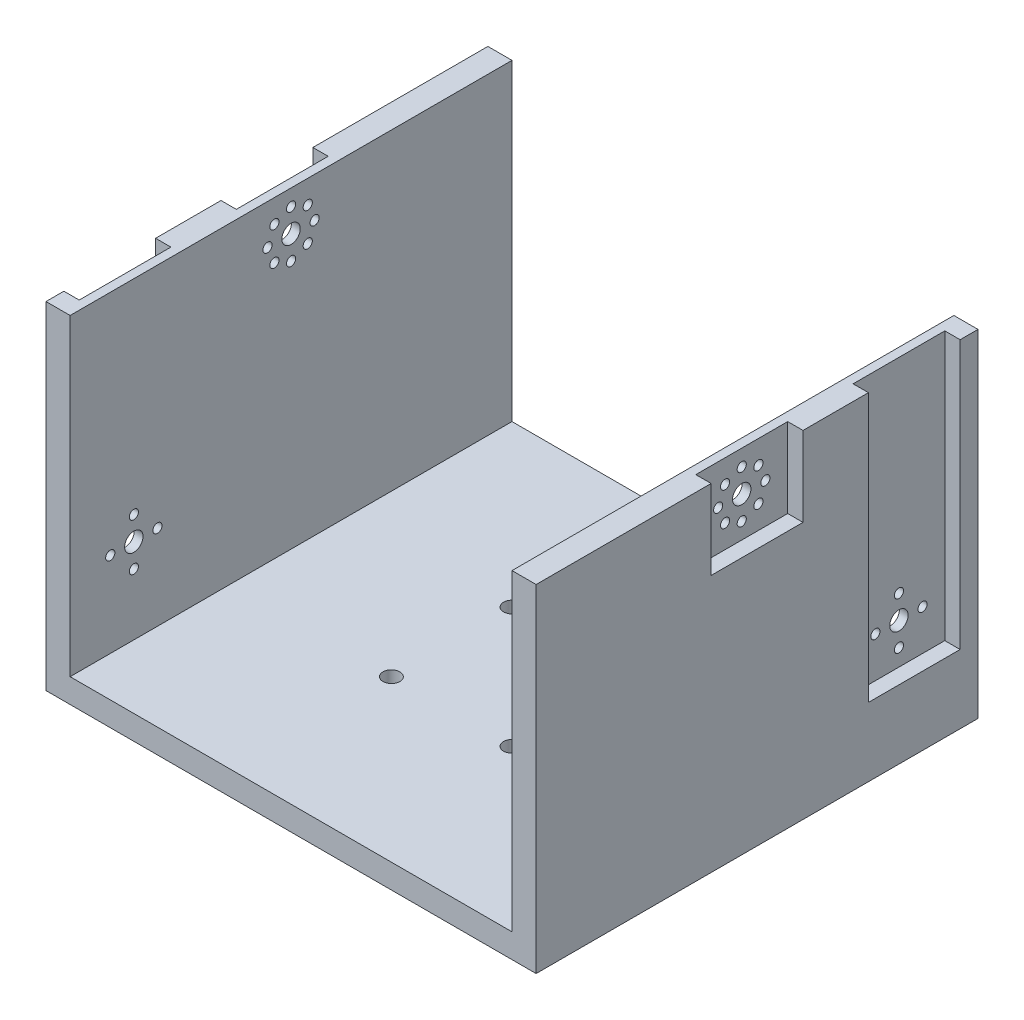
SolidWorks part; units mm, degrees
ref_plane "Front" through (0, 0, 0) normal (0, 0, 1) x (1, 0, 0)
ref_plane "Top" through (0, 0, 0) normal (0, 1, 0) x (1, 0, 0)
ref_plane "Right" through (0, 0, 0) normal (1, 0, 0) x (0, 0, -1)
sketch "Sketch2" plane through (0, 0, 0) normal (0, 1, 0) x (1, 0, 0)
  line L1 (-91.6, -91.6) -> (91.6, -91.6)
  line L2 (-91.6, -91.6) -> (-91.6, 91.6)
  line L3 (-91.6, 91.6) -> (91.6, 91.6)
  line L4 (91.6, -91.6) -> (91.6, 91.6)
  line L5 (-91.6, -91.6) -> (91.6, 91.6) construction
  line L6 (-91.6, 91.6) -> (91.6, -91.6) construction
  point P0 (0, 0)
  dimension "D1" = 183.2
extrude "Boss-Extrude1" add sketch "Sketch2" along normal blind 10
sketch "Sketch3" plane through (0, 0, 0) normal (0, 1, 0) x (1, 0, 0)
  line L0 (-91.6, -91.6) -> (91.6, -91.6) construction
  line L1 (-91.6, 91.6) -> (-101.6, 91.6)
  line L2 (-91.6, 91.6) -> (-91.6, -91.6)
  line L3 (-91.6, -91.6) -> (-101.6, -91.6)
  line L4 (-101.6, 91.6) -> (-101.6, -91.6)
  line L5 (0, 0) -> (0, 91.6) construction
  line L6 (91.6, 91.6) -> (-91.6, 91.6) construction
  line L7 (101.6, 91.6) -> (101.6, -91.6)
  line L8 (91.6, -91.6) -> (101.6, -91.6)
  line L9 (91.6, 91.6) -> (91.6, -91.6)
  line L10 (91.6, 91.6) -> (101.6, 91.6)
  dimension "D1" = 10
extrude "Boss-Extrude2" add sketch "Sketch3" along normal blind 139.7
sketch "Sketch4" plane through (0, 10, 0) normal (0, 1, 0) x (1, 0, 0)
  point P4 (0, 0)
hole_wizard "M6 Clearance Hole1" positions "Sketch5" profile "Sketch6" hole size "M6" standard "ANSI Metric" end condition up to next
sketch "Sketch5" plane through (0, 10, 0) normal (0, 1, 0) x (1, 0, 0)
  line L0 (0, 0) -> (0, 25) construction
  line L1 (0, 25) -> (-25, 25) construction
  line L3 (0, 25) -> (25, 25) construction
  point P0 (-25, 25)
  point P13 (25, 25)
  point P14 (25, -25)
  point P15 (-25, -25)
  dimension "D1" = 25
  dimension "D2" = 4
sketch "Sketch6" plane through (-25, 10, -25) normal (1, 0, 0) x (0, 0, 1)
  line L0 (0, 0) -> (0, 10)
  line L1 (0, 10) -> (3.5, 10)
  line L2 (3.5, 10) -> (3.5, 0)
  line L5 (3.5, 0) -> (0, 0)
  line L11 (0, -6.35) -> (0, 107.95) construction
  dimension "Thru Hole Dia." = 7
  dimension "Thru Hole Depth" = 10
sketch "Sketch7" plane through (91.6, 0, 0) normal (-1, 0, 0) x (0, 0, 1)
  line L0 (-91.6, 139.7) -> (91.6, 139.7) construction
  line L1 (0, 123.19) -> (0, 132.969) construction
  line L2 (0, 123.19) -> (0, 132.969) construction
  circle A0 centre (0, 123.19) radius 3.81
  circle A1 centre (0, 132.969) radius 1.8987
  circle A2 centre (6.9148, 130.1048) radius 1.8987
  circle A3 centre (9.779, 123.19) radius 1.8987
  circle A4 centre (6.9148, 116.2752) radius 1.8987
  circle A5 centre (0, 113.411) radius 1.8987
  circle A6 centre (-6.9148, 116.2752) radius 1.8987
  circle A7 centre (-9.779, 123.19) radius 1.8987
  circle A8 centre (-6.9148, 130.1048) radius 1.8987
  point P7 (0, 139.7)
  dimension "D1" = 7.62
  dimension "D3" = 3.7973
  dimension "D2" = 16.51
  dimension "D6" = 9.779
  dimension "D5" = 8
extrude "Cut-Extrude1" cut sketch "Sketch7" against normal through all both and the other way through all
sketch "Sketch8" plane through (0, 139.7, 0) normal (0, 1, 0) x (1, 0, 0)
  line L1 (95.25, -19.05) -> (101.6, -19.05)
  line L2 (95.25, -19.05) -> (95.25, 19.05)
  line L3 (95.25, 19.05) -> (101.6, 19.05)
  line L4 (101.6, -19.05) -> (101.6, 19.05)
  line L5 (95.25, -19.05) -> (101.6, 19.05) construction
  line L6 (95.25, 19.05) -> (101.6, -19.05) construction
  line L9 (101.6, -91.6) -> (101.6, 91.6) construction
  line L10 (0, 0) -> (0, 91.6) construction
  line L11 (91.6, 91.6) -> (-91.6, 91.6) construction
  line L13 (-95.25, 19.05) -> (-101.6, -19.05) construction
  line L14 (-95.25, -19.05) -> (-101.6, 19.05) construction
  line L16 (-101.6, -19.05) -> (-101.6, 19.05)
  line L17 (-95.25, 19.05) -> (-101.6, 19.05)
  line L18 (-95.25, -19.05) -> (-95.25, 19.05)
  line L19 (-95.25, -19.05) -> (-101.6, -19.05)
  point P0 (98.425, 0)
  point P12 (101.6, 0)
  point P23 (-98.425, 0)
  dimension "D1" = 38.1
  dimension "D2" = 6.35
extrude "Cut-Extrude2" cut sketch "Sketch8" against normal blind 33.02
sketch "Sketch9" plane through (101.6, 0, 0) normal (1, 0, 0) x (0, 0, -1)
  line L0 (48.666, 28.486) -> (54.762, 28.486) construction
  line L2 (84.186, 62.024) -> (84.186, 28.476)
  line L3 (84.186, 28.476) -> (46.166, 28.476)
  line L4 (46.166, 62.024) -> (46.166, 28.476)
  line L5 (84.186, 62.024) -> (46.166, 28.476) construction
  line L6 (84.186, 28.476) -> (46.166, 62.024) construction
  line L7 (48.666, 37.63) -> (48.666, 28.486) construction
  line L13 (84.186, 62.024) -> (84.186, 139.7)
  line L14 (19.05, 139.7) -> (91.6, 139.7) construction
  line L15 (84.186, 139.7) -> (46.166, 139.7)
  line L16 (46.166, 139.7) -> (46.166, 62.024)
  point P0 (65.176, 45.25)
  point P10 (65.176, 55.029)
  point P11 (55.397, 45.25)
  point P13 (65.176, 35.471)
  point P15 (74.955, 45.25)
  dimension "D1" = 0.01
  dimension "D2" = 2.5
extrude "Cut-Extrude3" cut sketch "Sketch9" against normal blind 6.35
sketch "Sketch11" plane through (95.25, 0, 0) normal (1, 0, 0) x (0, 0, -1)
  circle A0 centre (65.176, 45.25) radius 3.81
  circle A1 centre (0, 123.19) radius 3.81 construction
  point P0 (64.9555, 45.25)
  point P10 (0, 0)
extrude "Cut-Extrude4" cut sketch "Sketch11" against normal up to next
hole_wizard "#6 Clearance Hole1" positions "Sketch12" profile "Sketch13" hole size "#6" standard "ANSI Inch" end condition up to next
sketch "Sketch12" plane through (95.25, 0, 0) normal (1, 0, 0) x (0, 0, -1)
  point P0 (65.176, 55.029)
  point P3 (55.397, 45.25)
  point P6 (74.955, 45.25)
  point P10 (65.176, 35.471)
  point P16 (0, 0)
  point P17 (56.7668, 45.25)
  point P18 (52.2638, 45.6279)
  point P19 (55.1765, 45.25)
sketch "Sketch13" plane through (95.25, 55.029, -65.176) normal (0, 1, 0) x (0, 0, -1)
  line L0 (0, 0) -> (0, 3.65)
  line L1 (0, 3.65) -> (1.8986, 3.65)
  line L2 (1.8986, 3.65) -> (1.8986, 0)
  line L5 (1.8986, 0) -> (0, 0)
  line L11 (0, -6.35) -> (0, 107.95) construction
  dimension "Thru Hole Dia." = 3.7973
  dimension "Thru Hole Depth" = 3.65
ref_plane "Plane1" through (0, 0, 0) normal (-0.7071, 0, 0.7071) x (0.7071, 0, 0.7071)
ref_axis "Axis1" through (0, 0, 0) along (0, 1, 0)
pattern_circular "CirPattern1" count 2 over 360 about axis through (0, 0, 0) along (0, 1, 0) of "Cut-Extrude3", "Cut-Extrude4", "#6 Clearance Hole1"
